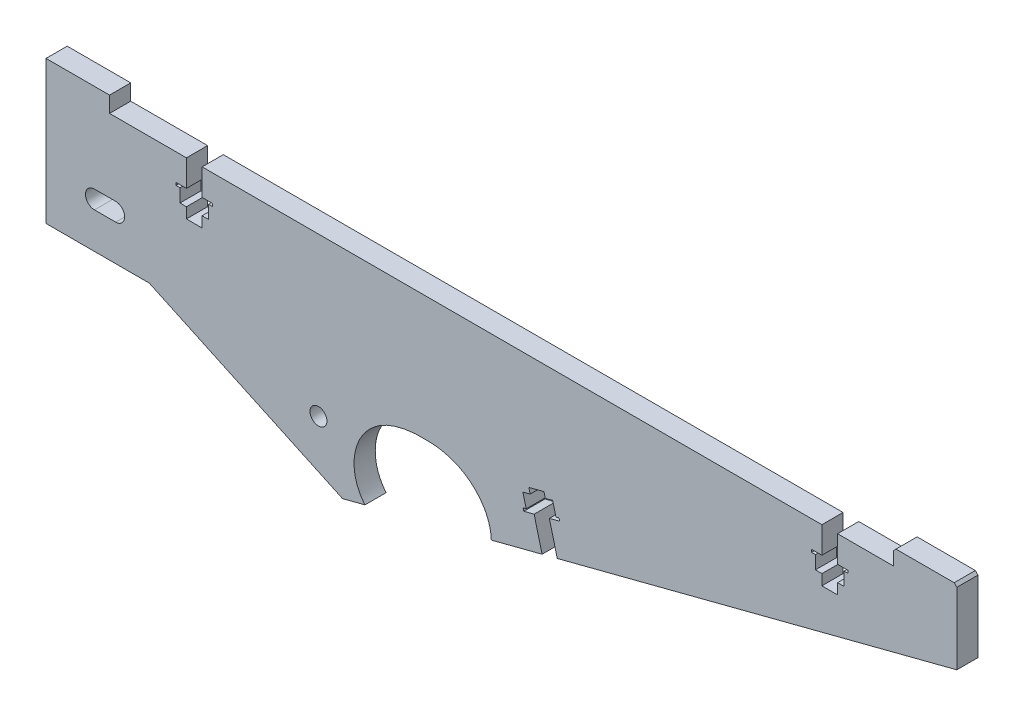
SolidWorks part; units mm, degrees
material "Oak"
ref_plane "Front Plane" through (0, 0, 0) normal (0, 0, 1) x (1, 0, 0)
ref_plane "Top Plane" through (0, 0, 0) normal (0, 1, 0) x (1, 0, 0)
ref_plane "Right Plane" through (0, 0, 0) normal (1, 0, 0) x (0, 0, -1)
sketch "Sketch2" plane through (0, 0, 0) normal (0, 1, 0) x (1, 0, 0)
  line L0 (70.6242, 37.5795) -> (117.4058, -50.3384) construction
  line L5 (206.8451, -8.3097) -> (157.7569, 83.9432) construction
  line L6 (157.7569, 83.9432) -> (0, 0) construction
  line L7 (-16.3156, 8.3097) -> (-2.2233, -18.1744) construction
  line L8 (-16.3156, 8.3097) -> (2.2233, 18.1744) construction
  line L9 (-2.2233, -18.1744) -> (16.3156, -8.3097) construction
  line L10 (2.2233, 18.1744) -> (16.3156, -8.3097) construction
  line L11 (-16.3156, 8.3097) -> (16.3156, -8.3097) construction
  line L12 (-2.2233, -18.1744) -> (2.2233, 18.1744) construction
  circle A0 centre (206.8451, -8.3097) radius 2 construction
  point P0 (70.6242, 37.5795)
  dimension "D2" = 4
  dimension "D1" = 80
  dimension "D3" = 30
  dimension "D4" = 21
  dimension "D5" = 104.5
  dimension "D6" = 178.7
ref_plane "Plane2" through (0, 0, 8.3097) normal (0, 0, 1) x (1, 0, 0)
sketch "Sketch1" plane through (0, 0, 8.3097) normal (0, 0, 1) x (1, 0, 0)
  line L0 (22.8451, -6) -> (22.8451, 18)
  line L1 (42.3451, -6) -> (78.8451, -23)
  line L2 (49.3651, 18) -> (49.3651, 13)
  line L3 (49.3651, 13) -> (47.3951, 13)
  line L4 (47.3951, 13) -> (47.3951, 12.5)
  line L5 (47.3951, 12.5) -> (48.1451, 12.5)
  line L6 (48.1451, 12.5) -> (48.1451, 10)
  line L7 (194.8451, 21) -> (194.8451, 7)
  line L8 (48.1451, 10) -> (49.3651, 10)
  line L9 (49.3651, 10) -> (49.3651, 8)
  line L10 (49.3651, 8) -> (52.3251, 8)
  line L11 (22.8451, 18) -> (22.8451, 21)
  line L12 (22.8451, 21) -> (34.8451, 21)
  line L13 (157.7569, 0) -> (0, 0) construction
  line L15 (22.8451, -6) -> (42.3451, -6)
  line L23 (52.3251, 10) -> (52.3251, 8)
  line L25 (53.5451, 10) -> (52.3251, 10)
  line L27 (78.8451, -23) -> (194.8451, 7)
  line L28 (53.5451, 12.5) -> (53.5451, 10)
  line L29 (54.2951, 12.5) -> (53.5451, 12.5)
  line L30 (170.8451, 18) -> (170.8451, 8) construction
  line L31 (169.3651, 18) -> (169.3651, 13)
  line L32 (169.3651, 13) -> (167.3951, 13)
  line L33 (167.3951, 13) -> (167.3951, 12.5)
  line L34 (167.3951, 12.5) -> (168.1451, 12.5)
  line L35 (168.1451, 12.5) -> (168.1451, 10)
  line L36 (168.1451, 10) -> (169.3651, 10)
  line L37 (169.3651, 10) -> (169.3651, 8)
  line L38 (169.3651, 8) -> (172.3251, 8)
  line L39 (172.3251, 10) -> (172.3251, 8)
  line L40 (173.5451, 10) -> (172.3251, 10)
  line L41 (173.5451, 12.5) -> (173.5451, 10)
  line L42 (174.2951, 12.5) -> (173.5451, 12.5)
  line L43 (54.2951, 13) -> (54.2951, 12.5)
  line L44 (52.3251, 13) -> (54.2951, 13)
  line L45 (34.8451, 21) -> (34.8451, 18)
  line L46 (34.8451, 18) -> (49.3651, 18)
  line L47 (52.3251, 18) -> (52.3251, 13)
  line L48 (50.8451, 18) -> (50.8451, 8) construction
  line L50 (169.3651, 18) -> (49.3651, 18) construction
  line L51 (174.2951, 13) -> (174.2951, 12.5)
  line L52 (172.3251, 13) -> (174.2951, 13)
  line L53 (172.3251, 18) -> (172.3251, 13)
  line L54 (172.3251, 18) -> (182.8451, 18)
  line L55 (52.3251, 18) -> (169.3651, 18)
  line L57 (182.8451, 18) -> (182.8451, 21)
  line L58 (182.8451, 21) -> (194.8451, 21)
  dimension "D1" = 19.5
  dimension "D7" = 2
  dimension "D4" = 24
  dimension "D5" = 148
  dimension "D6" = 24
  dimension "D8" = 120
  dimension "D9" = 6
  dimension "D10" = 14
  dimension "D11" = 116
  dimension "D12" = 30
  dimension "D27" = 10
  dimension "D28" = 2
  dimension "D29" = 0.5
  dimension "D30" = 2.5
  dimension "D31" = 2.96
  dimension "D33" = 6.9
  dimension "D34" = 5.4
  dimension "D36" = 12
  dimension "D37" = 3
extrude "Boss-Extrude1" add sketch "Sketch1" against normal blind 4
chamfer "Chamfer2" distance 0.5 angle 45 2 edges at (194.8451, 21, 6.3097) (182.8451, 21, 6.3097)
ref_axis "Axis1" through (0, -24.2941, 0) along (0, 1, 0)
ref_plane "Plane1" through (0, 0, 0) normal (0.4697, 0, 0.8828) x (0.8828, 0, -0.4697)
ref_plane "Plane3" through (0, 0, 6.3097) normal (0, 0, 1) x (1, 0, 0)
sketch "Sketch3" plane through (0, 0, 0) normal (0.4697, 0, 0.8828) x (0.8828, 0, -0.4697)
  line L0 (41.5552, 18) -> (28.7369, 18) construction
  circle A0 centre (80, -16) radius 10.5
  dimension "D2" = 21
  dimension "D1" = 80
  dimension "D3" = 34
extrude "Cut-Extrude3" cut sketch "Sketch3" along normal through all
sketch "Sketch8" plane through (0, 0, 6.3097) normal (0, 0, 1) x (1, 0, 0)
  line L0 (83.0789, -21.9051) -> (106.9323, -15.7361)
  ellipse E0 centre (92.9137, -16) end of major axis (81.0197, -16) minor radius 10.5 (104.8032, -16.2867) -> (83.0789, -21.9051) ccw construction
  ellipse E1 centre (95.0421, -16) end of major axis (83.1482, -16) minor radius 10.5 (106.9323, -15.7361) -> (84.8702, -21.4418) ccw construction
  spline S0 degree 3 poles (83.0789, -21.9051) (80.533, -18.9105) (80.4177, -12.548) (86.1771, -6.6365) (91.2081, -5.4527) (95.8369, -5.4739) (99.8427, -6.0135) (104.9141, -9.1613) (106.8844, -13.221) (106.9323, -15.7361) knots 0 0 0 0 0.257216 0.380775 0.549932 0.599416 0.70468 0.827401 1 1 1 1
extrude "Cut-Extrude4" cut sketch "Sketch8" against normal blind 10 and the other way blind 10
sketch "Sketch9" plane through (0, 0, 8.3097) normal (0, 0, 1) x (1, 0, 0)
  line L0 (32, 2.5) -> (36, 2.5) construction
  line L1 (32, 4.2) -> (36, 4.2)
  line L2 (32, 0.8) -> (36, 0.8)
  arc A0 (32, 4.2) -> (32, 0.8) centre (32, 2.5) ccw
  arc A1 (36, 0.8) -> (36, 4.2) centre (36, 2.5) ccw
  point P2 (34, 2.5)
  dimension "D2" = 1.7
  dimension "D1" = 34
  dimension "D3" = 4
  dimension "D4" = 2.5
extrude "Cut-Extrude5" cut sketch "Sketch9" against normal through all
ref_point "Point1"
sketch "Sketch10" plane through (0, 0, 8.3097) normal (0, 0, 1) x (1, 0, 0)
  line L0 (117.9616, -12.8837) -> (115.4577, -3.2022) construction
  line L1 (106.9323, -15.7361) -> (194.8451, 7) construction
  line L2 (119.3944, -12.5131) -> (117.8921, -6.7042)
  line L3 (117.8921, -6.7042) -> (119.8478, -6.1984)
  line L4 (119.8478, -6.1984) -> (119.7226, -5.7144)
  line L5 (119.7226, -5.7144) -> (119.1417, -5.8646)
  line L6 (119.1417, -5.8646) -> (118.5158, -3.4442)
  line L7 (118.5158, -3.4442) -> (117.141, -3.7998)
  line L8 (117.141, -3.7998) -> (116.8906, -2.8316)
  line L9 (116.8906, -2.8316) -> (114.0249, -3.5728)
  line L10 (116.5287, -13.2542) -> (119.3944, -12.5131)
  line L12 (114.2753, -4.5409) -> (114.0249, -3.5728)
  line L13 (112.9005, -4.8965) -> (114.2753, -4.5409)
  line L14 (113.5265, -7.3168) -> (112.9005, -4.8965)
  line L15 (112.9456, -7.4671) -> (113.5265, -7.3168)
  line L16 (113.0708, -7.9511) -> (112.9456, -7.4671)
  line L17 (115.0264, -7.4454) -> (113.0708, -7.9511)
  line L18 (116.5287, -13.2542) -> (115.0264, -7.4454)
  line L19 (83.0789, -21.9051) -> (106.9323, -15.7361) construction
  line L20 (93.9779, 0) -> (93.9779, -16) construction
  line L21 (93.9779, -16) -> (91.7244, -7.2867) construction
  line L22 (74.2978, -11.7936) -> (91.7244, -7.2867) construction
  circle A0 centre (74.2978, -11.7936) radius 1.6
  point P26 (98.3046, -17.9674)
  dimension "D8" = 3.2
  dimension "D10" = 18
  dimension "D1" = 10
  dimension "D2" = 2.96
  dimension "D3" = 5.8
  dimension "D4" = 7
  dimension "D5" = 0.5
  dimension "D6" = 2.5
  dimension "D7" = 1
  dimension "D9" = 24
  dimension "D11" = 16
  dimension "D12" = 2.988
  dimension "D13" = 9
extrude "Cut-Extrude6" cut sketch "Sketch10" against normal through all
equation "\"bed-plate-thickness\"=3"
equation "\"D1@Boss-Extrude1\"=\"y-cross-rib-thickness\""
equation "\"D37@Sketch1\" = \"bed-plate-thickness\""
equation "\"y-cross-rib-thickness\"=4"
equation "\"y-rib-thickness\"=6"
equation "\"x-plate-thickness\"=5"
equation "\"rod-diameter\"=12"
equation "\"t-nut-hole-diameter\"=3"
equation "\"D5@Sketch2\"=209/2"
